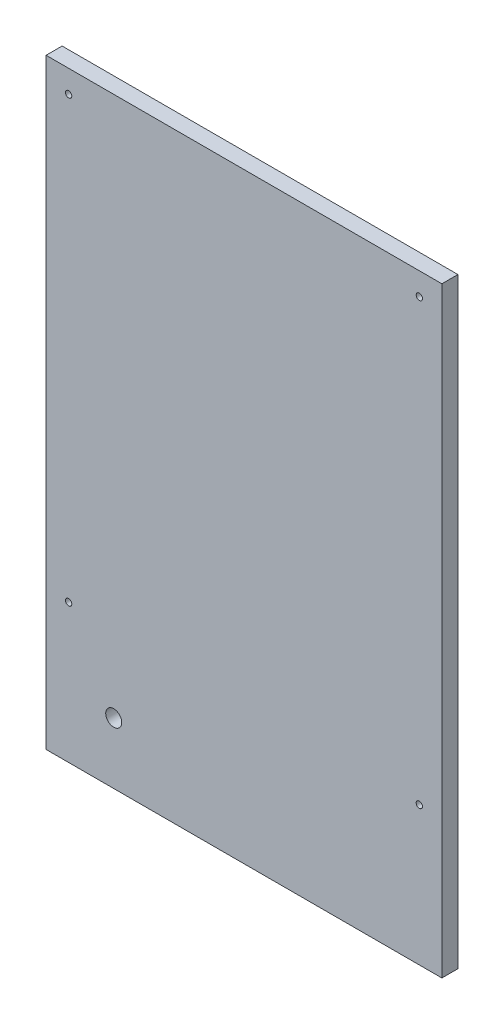
SolidWorks part; units mm, degrees
ref_plane "Front Plane" through (0, 0, 0) normal (0, 0, 1) x (1, 0, 0)
ref_plane "Top Plane" through (0, 0, 0) normal (0, 1, 0) x (1, 0, 0)
ref_plane "Right Plane" through (0, 0, 0) normal (1, 0, 0) x (0, 0, -1)
sketch "Sketch1" plane through (0, 0, 0) normal (0, 0, 1) x (1, 0, 0)
  line L1 (0, 0) -> (395, 0)
  line L2 (0, 0) -> (0, 600)
  line L3 (0, 600) -> (395, 600)
  line L4 (395, 0) -> (395, 600)
  dimension "D1" = 600
  dimension "D2" = 395
extrude "Base" add sketch "Sketch1" along normal blind 16
sketch "Sketch2" plane through (0, 0, 16) normal (0, 0, 1) x (1, 0, 0)
  line L0 (197.5, 600) -> (197.5, 0) construction
  line L1 (22.5, 577.5) -> (0, 577.5) construction
  line L2 (0, 600) -> (0, 0) construction
  line L3 (395, 600) -> (0, 600) construction
  line L4 (22.5, 577.5) -> (22.5, 600) construction
  line L5 (22.5, 600) -> (22.5, 0) construction
  line L6 (0, 0) -> (395, 0) construction
  line L8 (395, 300) -> (0, 300) construction
  line L9 (395, 0) -> (395, 600) construction
  line L10 (0, 600) -> (0, 0) construction
  circle A0 centre (22.5, 577.5) radius 3.15
  circle A1 centre (372.5, 577.5) radius 3.15
  circle A2 centre (22.5, 138.5) radius 3.15
  circle A3 centre (372.5, 138.5) radius 3.15
  dimension "D1" = 6.3
  dimension "D2" = 350
  dimension "D3" = 138.5
extrude "Mounting holes" cut sketch "Sketch2" against normal through all
sketch "Sketch3" [suppressed] plane through (0, 0, 0) normal (0, 0, -1) x (-1, 0, 0)
  line L0 (-395, 600) -> (0, 0) construction
  line L1 (-395, 0) -> (0, 600) construction
  line L2 (-395, 0) -> (-395, 600) construction
  line L3 (-356.5, 38.5) -> (-38.5, 38.5)
  line L4 (-356.5, 38.5) -> (-356.5, 561.5)
  line L5 (-356.5, 561.5) -> (-38.5, 561.5)
  line L6 (-38.5, 38.5) -> (-38.5, 561.5)
  line L7 (-356.5, 38.5) -> (-38.5, 561.5) construction
  line L8 (-356.5, 561.5) -> (-38.5, 38.5) construction
  line L9 (-356.5, 300) -> (-395, 300) construction
  line L10 (-197.5, 561.5) -> (-197.5, 600) construction
  line L11 (-395, 600) -> (0, 600) construction
  line L12 (-57.75, 38.5) -> (-57.75, 77) construction
  line L13 (-38.5, 38.5) -> (-356.5, 38.5)
  line L14 (-38.5, 38.5) -> (-38.5, 77)
  line L15 (-38.5, 77) -> (-356.5, 77)
  line L16 (-356.5, 38.5) -> (-356.5, 77)
  line L17 (-77, 57.75) -> (-38.5, 57.75) construction
  line L18 (-38.5, 38.5) -> (-77, 38.5)
  line L19 (-38.5, 38.5) -> (-38.5, 77)
  line L20 (-38.5, 77) -> (-77, 77)
  line L21 (-77, 38.5) -> (-77, 77)
  point P8 (-197.5, 300)
  point P29 (-57.75, 57.75)
  dimension "D1" = 38.5
extrude "Center hole" [suppressed] cut sketch "Sketch3" against normal up to next contours L15 L6 L5 L4 | L21 L13 L6 L15
sketch "Sketch4" plane through (0, 0, 0) normal (0, 0, -1) x (-1, 0, 0)
  line L0 (-45, 600) -> (-45, 0) construction
  line L2 (0, 0) -> (-395, 0) construction
  line L3 (-395, 38.5) -> (0, 38.5) construction
  line L4 (-395, 0) -> (-395, 600) construction
  line L5 (0, 600) -> (0, 0) construction
  line L6 (-22.5, 577.5) -> (-22.5, 600) construction
  line L7 (-395, 600) -> (0, 600) construction
  line L8 (0, 0) -> (-395, 0) construction
  line L10 (-90, 61) -> (-45, 61) construction
  line L11 (-45, 300) -> (0, 300) construction
  line L12 (0, 600) -> (0, 0) construction
  line L13 (-45, 38.5) -> (-90, 38.5)
  line L14 (-45, 38.5) -> (-45, 83.5)
  line L15 (-45, 83.5) -> (-90, 83.5)
  line L16 (-90, 38.5) -> (-90, 83.5)
  line L17 (-67.5, 83.5) -> (-67.5, 38.5) construction
  line L18 (-45, 577.5) -> (0, 577.5) construction
  circle A0 centre (-67.5, 61) radius 8
  point P34 (0, 0)
  dimension "D3" = 16
  dimension "D1" = 38.5
extrude "Tap hole" cut sketch "Sketch4" against normal up to next contours A0 region at (67.5, 61, 0)
equation "\"D2@Sketch2\"=50*7"
equation "\"D1@Sketch3\"=2*19.25"
